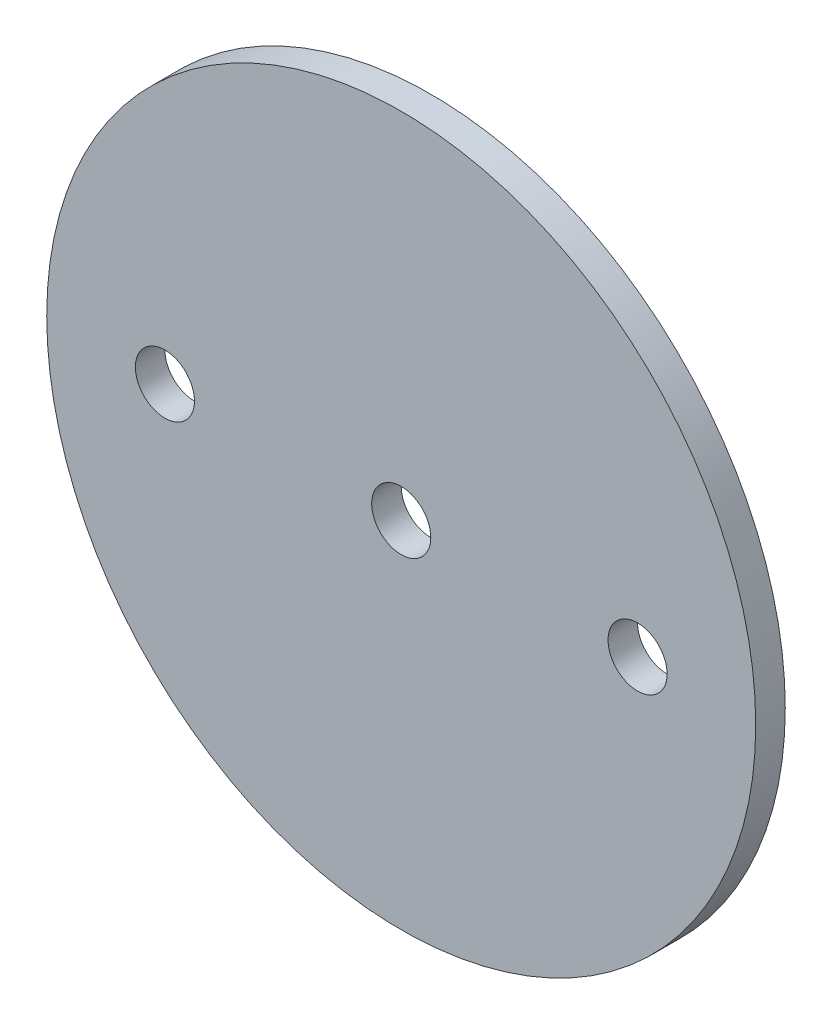
SolidWorks part; units mm, degrees
ref_plane "Front Plane" through (0, 0, 0) normal (0, 0, 1) x (1, 0, 0)
ref_plane "Top Plane" through (0, 0, 0) normal (0, 1, 0) x (1, 0, 0)
ref_plane "Right Plane" through (0, 0, 0) normal (1, 0, 0) x (0, 0, -1)
sketch "Sketch1" plane through (0, 0, 0) normal (0, 0, 1) x (1, 0, 0)
  circle A0 centre (0, 0) radius 38.1
extrude "Boss-Extrude1" add sketch "Sketch1" along normal mid plane 3.175
sketch "Sketch2" plane through (0, 0, 1.5875) normal (0, 0, 1) x (1, 0, 0)
  line L0 (-1000, 0) -> (49000, 0) construction
  point P1 (0, 0)
  point P4 (25.4, 0)
  point P5 (-25.4, 0)
  dimension "D1" = 25.4
  dimension "D2" = 50.8
hole_wizard "1/4 (0.25) Diameter Hole1" positions "Sketch2" profile "Sketch3" hole size "1/4" standard "ANSI Inch" end condition through all
sketch "Sketch3" plane through (-25.4, 0, 1.5875) normal (1, 0, 0) x (0, -1, 0)
  line L0 (0, 0) -> (0, 3.175)
  line L1 (0, 3.175) -> (3.175, 3.175)
  line L2 (3.175, 3.175) -> (3.175, 0)
  line L5 (3.175, 0) -> (0, 0)
  line L11 (0, -6.35) -> (0, 107.95) construction
  dimension "Thru Hole Dia." = 6.35
  dimension "Thru Hole Depth" = 3.175
equation "\"AIRFRAME_OD\"= 3.142in"
equation "\"AIRFRAME_ID\"= 3.00in"
equation "\"FLAT_T\"= 0.125in"
equation "\"NOSE_EXP_L\"= 3.5in"
equation "\"NOSE_SHOULDER_L\"= 1.5in"
equation "\"MAIN_L\"= 30in"
equation "\"RECO_COUP_L\"= 6in"
equation "\"RECO_SWITCH_L\"= 1.5in"
equation "\"DROGUE_L\"= 14in"
equation "\"ATS_FORE_COUP_L\"= 4in"
equation "\"ATS_AFT_COUP_L\"= 2.5in"
equation "\"LOWER_L\"= 16in"
equation "\"FIN_N\"= 4"
equation "\"CR_AFT_X\"= 0.5in"
equation "\"CR_FORE_X\"= 6in"
equation "\"FIN_ROOT\"= 5in"
equation "\"FIN_X\"= 0.75in"
equation "\"MOTOR_OD\"= 2.25in"
equation "\"MOTOR_ID\"= 2.126in"
equation "\"COUPLER_OD\"= 2.998in"
equation "\"COUPLER_ID\"= 2.875in"
equation "\"D1@Sketch1\"=\"AIRFRAME_ID\""
equation "\"D1@Boss-Extrude1\"=\"FLAT_T\""
equation "\"RECO_ROD_X\"= 1.5in"
equation "\"ATS_ROD_X\"= 2in"
equation "\"D1@Sketch2\"=\"ATS_ROD_X\"*0.5"
equation "\"D2@Sketch2\"=\"ATS_ROD_X\""
